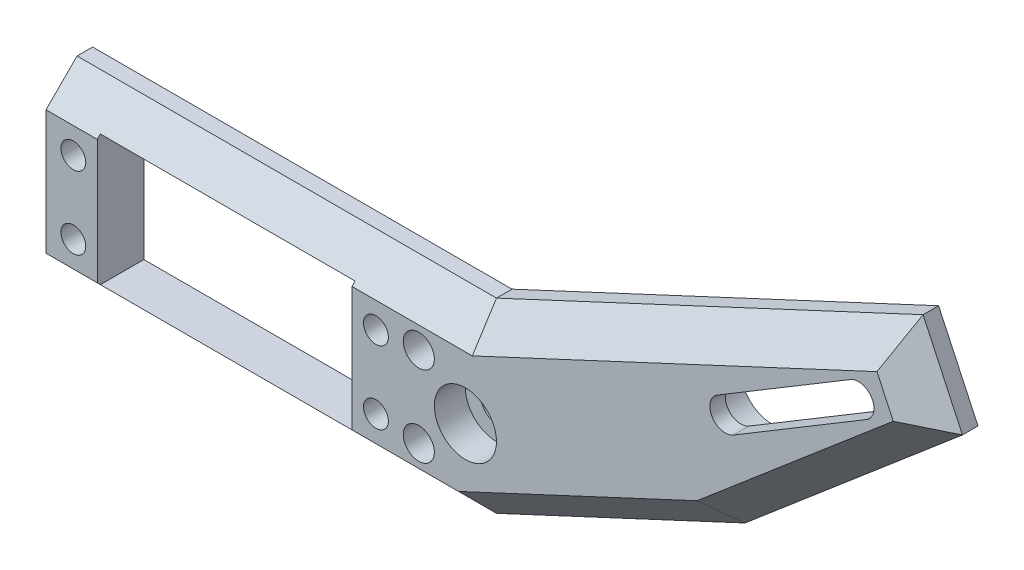
SolidWorks part; units mm, degrees
ref_plane "前视基准面" through (0, 0, 0) normal (0, 0, 1) x (1, 0, 0)
ref_plane "上视基准面" through (0, 0, 0) normal (0, 1, 0) x (1, 0, 0)
ref_plane "右视基准面" through (0, 0, 0) normal (1, 0, 0) x (0, 0, -1)
other "Configuration Table"
sketch "Sketch1" plane through (0, 0, 0) normal (0, 0, 1) x (1, 0, 0)
  line L1 (-28.75, -15) -> (28.75, -15)
  line L2 (-28.75, -15) -> (-28.75, 15)
  line L3 (-28.75, 15) -> (28.75, 15)
  line L4 (28.75, -15) -> (28.75, 15)
  line L5 (-28.75, -15) -> (28.75, 15) construction
  line L6 (-28.75, 15) -> (28.75, -15) construction
  point P0 (0, 0)
  dimension "D1" = 57.5
  dimension "D2" = 30
extrude "Boss-Extrude1" add sketch "Sketch1" along normal blind 30
sketch "Sketch2" plane through (0, 0, 30) normal (0, 0, 1) x (1, 0, 0)
  line L1 (-20.5, -10.5) -> (20.5, -10.5)
  line L2 (-20.5, -10.5) -> (-20.5, 10.5)
  line L3 (-20.5, 10.5) -> (20.5, 10.5)
  line L4 (20.5, -10.5) -> (20.5, 10.5)
  line L5 (-20.5, -10.5) -> (20.5, 10.5) construction
  line L6 (-20.5, 10.5) -> (20.5, -10.5) construction
  point P0 (0, 0)
  dimension "D1" = 41
  dimension "D2" = 21
extrude "Cut-Extrude1" cut sketch "Sketch2" against normal blind 25
ref_plane "Plane1" through (0, 0, 15) normal (0, 0, 1) x (1, 0, 0)
sketch "Sketch8" plane through (0, 0, 30) normal (0, 0, 1) x (1, 0, 0)
  line L0 (0, 0) -> (24.35, 0) construction
  line L1 (24.35, 0) -> (24.35, 5.85) construction
  line L2 (0, 0) -> (0, 15) construction
  line L3 (28.75, 15) -> (-28.75, 15) construction
  circle A0 centre (24.35, 5.85) radius 2
  circle A1 centre (24.35, -5.85) radius 2
  circle A2 centre (-24.35, -5.85) radius 2
  circle A3 centre (-24.35, 5.85) radius 2
  dimension "D3" = 4
  dimension "D1" = 5.85
  dimension "D2" = 24.35
extrude "Cut-Extrude6" cut sketch "Sketch8" against normal blind 10
sketch "Sketch10" plane through (0, 0, 5) normal (0, 0, 1) x (1, 0, 0)
  line L0 (0, 0) -> (-10, 0) construction
  circle A0 centre (-10, 0) radius 5
  dimension "D2" = 10
  dimension "D1" = 10
extrude "Cut-Extrude8" cut sketch "Sketch10" against normal blind 10
sketch "Sketch11" plane through (28.75, 0, 0) normal (1, 0, 0) x (0, 0, -1)
  line L0 (-30, 0) -> (0, 0) construction
  line L1 (-30, -15) -> (-30, 15) construction
  line L2 (0, 0) -> (-15, 0) construction
  line L3 (-15, -15) -> (-15, 15)
  line L4 (-30, 15) -> (0, 15) construction
  line L5 (-15, 15) -> (-11.75, 15)
  line L6 (-11.75, 15) -> (-11.75, 22.5)
  line L7 (-11.75, 22.5) -> (-18.25, 22.5)
  line L8 (-18.25, 22.5) -> (-18.25, 15)
  line L9 (-18.25, 15) -> (-15, 15)
  line L10 (7.5, 3.25) -> (0, 3.25)
  line L11 (0, 3.25) -> (0, 0)
  line L12 (0, -3.25) -> (7.5, -3.25)
  line L13 (0, 0) -> (0, -3.25)
  line L14 (7.5, -3.25) -> (7.5, 3.25)
  line L15 (-11.75, -22.5) -> (-11.75, -15)
  line L16 (-11.75, -15) -> (-15, -15)
  line L17 (-18.25, -15) -> (-18.25, -22.5)
  line L18 (-15, -15) -> (-18.25, -15)
  line L19 (-18.25, -22.5) -> (-11.75, -22.5)
  line L20 (-37.5, -3.25) -> (-30, -3.25)
  line L21 (-30, -3.25) -> (-30, 0)
  line L22 (-30, 3.25) -> (-37.5, 3.25)
  line L23 (-30, 0) -> (-30, 3.25)
  line L24 (-37.5, 3.25) -> (-37.5, -3.25)
  circle A0 centre (-15, 0) radius 7.5 construction
  point P12 (-15, 0)
  point P34 (-15, 0)
  line M5 (0, -15) -> (0, 15)
  line M6 (0, 15) -> (-30, 15)
  line M7 (-30, 15) -> (-30, -15)
  line M8 (-30, -15) -> (0, -15)
  dimension "D1" = 15
  dimension "D2" = 6.5
  dimension "D3" = 7.5
  dimension "D4" = 4
extrude "Boss-Extrude2" [suppressed] add sketch "Sketch11" against normal up to surface (8.25 mm away) contours L22 L24 L20 M7 | L17 L19 L15 M8 | L12 L14 L10 M5 | L7 L8 L6 M6
sketch "Sketch12" plane through (28.75, 0, 0) normal (1, 0, 0) x (0, 0, -1)
  line L20 (-36.5, 15) -> (-30, 15)
  line L21 (-30, -15) -> (-30, -21.5)
  line L22 (0, -15) -> (-11.75, -15)
  line L23 (0, 3.25) -> (0, 15)
  line L40 (0, -15) -> (0, 15)
  line L45 (0, 15) -> (-30, 15)
  line L50 (-30, 15) -> (-30, -15)
  line L55 (-30, -15) -> (0, -15)
  line L60 (0, -15) -> (0, 15)
  line L65 (0, 15) -> (-30, 15)
  line L70 (-30, 15) -> (-30, -15)
  line L75 (-30, -15) -> (0, -15)
  dimension "D1" = 0
extrude "Boss-Extrude3" [suppressed] add sketch "Sketch12" along normal blind 30
sketch "Sketch13" plane through (0, 0, 30) normal (0, 0, 1) x (1, 0, 0)
  line L0 (28.75, 15) -> (38.75, 15)
  line L1 (38.75, 15) -> (107.4107, 47.017)
  line L3 (113.75, 33.4224) -> (78.75, 3.6523)
  line L4 (78.75, 3.6523) -> (38.75, -15)
  line L5 (38.75, -15) -> (28.75, -15)
  line L6 (-28.75, -15) -> (28.75, -15) construction
  line L7 (38.75, 15) -> (38.75, -15) construction
  line L8 (38.75, -15) -> (93.0307, -15) construction
  line L9 (78.75, 3.6523) -> (97.9021, 3.6523) construction
  line L10 (38.75, 15) -> (83.4484, 15) construction
  line L11 (28.75, -15) -> (28.75, 15)
  line L12 (107.4107, 47.017) -> (113.75, 33.4224)
  dimension "D1" = 10
  dimension "D2" = 25
  dimension "D3" = 40
  dimension "D4" = 25
  dimension "D5" = 15
  dimension "D6" = 75
extrude "Boss-Extrude4" add sketch "Sketch13" against normal blind 30
sketch "Sketch16" plane through (1.1757, -2.5212, 0) normal (-0.4226, 0.9063, 0) x (0.9063, 0.4226, 0)
  line L0 (117.2174, -15) -> (97.2174, -15) construction
  line L1 (117.2174, 0) -> (117.2174, -30) construction
  line L2 (-16.5, -15) -> (16.5, -15) construction
  line L3 (97.2174, -15) -> (74.7174, -15) construction
  line L4 (67.2174, -15) -> (82.2174, -15) construction
  line L5 (67.2174, -12.5) -> (82.2174, -12.5)
  line L6 (67.2174, -17.5) -> (82.2174, -17.5)
  circle A0 centre (97.2174, -15) radius 5
  arc A1 (67.2174, -12.5) -> (67.2174, -17.5) centre (67.2174, -15) ccw
  arc A2 (82.2174, -17.5) -> (82.2174, -12.5) centre (82.2174, -15) ccw
  point P10 (74.7174, -15)
  dimension "D1" = 10
  dimension "D4" = 2.5
  dimension "D2" = 20
  dimension "D3" = 15
  dimension "D5" = 22.5
extrude "Cut-Extrude10" cut sketch "Sketch16" against normal blind 30
chamfer "Chamfer5" distance 5 angle 45 13 edges at (-28.75, 0, 0) (5, -15, 0) (58.75, -5.6738, 0) (96.25, 18.5374, 0) (110.5804, 40.2197, 0) (73.0804, 31.0085, 0) (5, 15, 0) (5, -15, 30) (58.75, -5.6738, 30) (96.25, 18.5374, 30) (73.0804, 31.0085, 30) (5, 15, 30) (110.5804, 40.2197, 30)
sketch "Sketch19" plane through (0, 0, 30) normal (0, 0, 1) x (1, 0, 0)
  line L0 (38.75, 15) -> (38.75, -15) construction
  line L1 (38.75, -15) -> (38.75, 0) construction
  line L2 (38.75, 0) -> (31.25, 0) construction
  line L3 (31.25, 0) -> (31.25, 6.5) construction
  circle A1 centre (38.75, 0) radius 2.5
  circle A2 centre (31.25, 6.5) radius 2.5
  circle A4 centre (31.25, -6.5) radius 2.5
  dimension "D1" = 5
  dimension "D2" = 5
  dimension "D3" = 7.5
  dimension "D4" = 6.5
extrude "Cut-Extrude12" cut sketch "Sketch19" against normal blind 30
sketch "Sketch20" plane through (0, 0, 5) normal (0, 0, 1) x (1, 0, 0)
  circle A0 centre (-10, 0) radius 7.5
  dimension "D1" = 15
extrude "Cut-Extrude13" cut sketch "Sketch20" against normal blind 2.5
sketch "Sketch29" plane through (0, 15, 0) normal (0, 1, 0) x (1, 0, 0)
  line L5 (-28.75, -30) -> (-28.75, -22.5)
  line L6 (-28.75, -25) -> (-28.75, -5) construction
  line L7 (-28.75, -22.5) -> (113.75, -22.5)
  line L8 (113.75, -5) -> (113.75, -25) construction
  line L9 (113.75, -22.5) -> (113.75, -30)
  line L10 (113.75, -30) -> (-28.75, -30)
  line L11 (-28.75, -22.5) -> (-28.75, 0)
  line L12 (-28.75, 0) -> (113.75, 0)
  line L13 (113.75, 0) -> (113.75, -22.5)
  line M5 (38.75, -5) -> (-28.75, -5)
  line M8 (38.75, -25) -> (38.75, -5)
  line M9 (-28.75, -5) -> (-28.75, -25)
  dimension "D1" = 7.5
extrude "Cut-Extrude15" cut sketch "Sketch29" against normal through all both and the other way through all contours L7 M9 M8 M5 | L13 L12 L11 L7 M5 M8 region at (5, 15, 13.75) region at (64.375, 15, 9.7917)
sketch "Sketch30" plane through (0, 0, 30) normal (0, 0, 1) x (1, 0, 0)
  line L0 (106.3003, 37.5674) -> (125.3057, 37.5674) construction
  line L1 (0, 0) -> (13.5097, 0) construction
  line L3 (107.6082, 34.7624) -> (104.9923, 40.3724) construction
  line L4 (106.3003, 37.5674) -> (102.0144, 34.9922) construction
  line L6 (80.5852, 22.1163) -> (102.0144, 34.9922) construction
  line L7 (79.2976, 24.2592) -> (100.7268, 37.1351)
  line L8 (81.8728, 19.9734) -> (103.302, 32.8493)
  arc A1 (79.2976, 24.2592) -> (81.8728, 19.9734) centre (80.5852, 22.1163) ccw
  arc A2 (103.302, 32.8493) -> (100.7268, 37.1351) centre (102.0144, 34.9922) ccw
  point P4 (91.2998, 28.5543)
  dimension "D1" = 2.5
  dimension "D2" = 25
  dimension "D3" = 5
  dimension "D4" = 149
extrude "Cut-Extrude16" cut sketch "Sketch30" against normal through all
sketch "Sketch31" plane through (0, 0, 30) normal (0, 0, 1) x (1, 0, 0)
  line L0 (102.0144, 34.9922) -> (80.5852, 22.1163) construction
  line L1 (104.5896, 30.7064) -> (83.1604, 17.8304)
  line L2 (99.4392, 39.2781) -> (78.01, 26.4021)
  arc A0 (104.5896, 30.7064) -> (99.4392, 39.2781) centre (102.0144, 34.9922) ccw
  arc A1 (78.01, 26.4021) -> (83.1604, 17.8304) centre (80.5852, 22.1163) ccw
  point P4 (91.2998, 28.5543)
  dimension "D1" = 5
extrude "Cut-Extrude17" [suppressed] cut sketch "Sketch31" against normal blind 5
ref_axis "Axis1" through (38.75, 0, 23.5478) along (0, 0, 1)
sketch "Sketch32" plane through (0, 0, 30) normal (0, 0, 1) x (1, 0, 0)
  circle A0 centre (38.75, 0) radius 5
  dimension "D1" = 10
extrude "Cut-Extrude18" cut sketch "Sketch32" against normal blind 5
sketch "Sketch36" plane through (0, 0, 22.5) normal (0, 0, -1) x (-1, 0, 0)
  line L0 (-102.0144, 34.9922) -> (-80.5852, 22.1163) construction
  line L1 (-99.4392, 39.2781) -> (-78.01, 26.4021)
  line L2 (-104.5896, 30.7064) -> (-83.1604, 17.8304)
  arc A0 (-99.4392, 39.2781) -> (-104.5896, 30.7064) centre (-102.0144, 34.9922) ccw
  arc A1 (-83.1604, 17.8304) -> (-78.01, 26.4021) centre (-80.5852, 22.1163) ccw
  point P4 (-91.2998, 28.5543)
  dimension "D1" = 5
extrude "Cut-Extrude19" cut sketch "Sketch36" against normal blind 5
